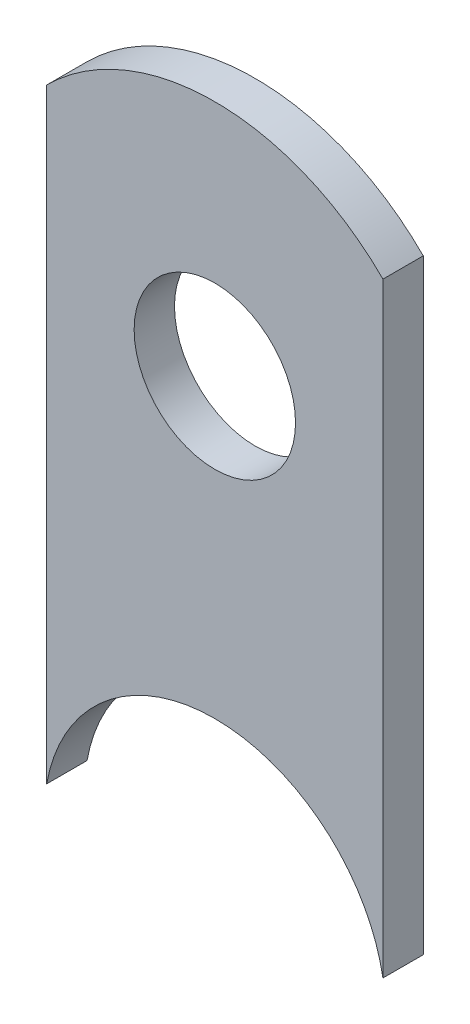
SolidWorks part; units mm, degrees
ref_plane "Front Plane" through (0, 0, 0) normal (0, 0, 1) x (1, 0, 0)
ref_plane "Top Plane" through (0, 0, 0) normal (0, 1, 0) x (1, 0, 0)
ref_plane "Right Plane" through (0, 0, 0) normal (1, 0, 0) x (0, 0, -1)
sketch "Sketch1" plane through (0, 0, 0) normal (0, 0, 1) x (1, 0, 0)
  line L2 (-12.5, 22.5) -> (-12.5, -22.5)
  line L4 (12.5, 22.5) -> (12.5, -22.5)
  line L5 (-12.5, 22.5) -> (12.5, -22.5) construction
  line L6 (-12.5, -22.5) -> (12.5, 22.5) construction
  arc A0 (-12.5, 22.5) -> (12.5, 22.5) centre (0, 10) cw
  arc A1 (-12.5, -22.5) -> (12.5, -22.5) centre (0, -24.745) cw
  circle A2 centre (0, 10) radius 6
  point P0 (0, 0)
  dimension "D1" = 45
  dimension "D3" = 12.7
  dimension "D4" = 12
  dimension "D2" = 25
base flange "Base-Flange1" sketch "Sketch1" thickness 3 reverse thickness direction no parameters "D1"=0.7366
sketch "Bend-Lines1" [suppressed] plane through (0, 0, 0) normal (0, 1, 0) x (1, 0, 0)
sketch "Bounding-Box1" [suppressed] plane through (0, 0, 0) normal (0, 1, 0) x (1, 0, 0)
sheet metal parameters "Sheet-Metal2" thickness 3 parameters "D1"=0.7366
flat pattern "Flat-Pattern2" [suppressed]
sketch "Bend-Lines2" plane through (0, 0, 0) normal (0, 1, 0) x (1, 0, 0)
sketch3d "Bounding-Box2" [suppressed]
  line L0 (-12.5, 2.245, 0) -> (-12.5, 52.4227, 0) construction
  line L1 (12.5, 2.245, 0) -> (12.5, 52.4227, 0) construction
  line L2 (-12.5, 2.245, 0) -> (12.5, 2.245, 0) construction
  line L3 (-12.5, 52.4227, 0) -> (12.5, 52.4227, 0) construction
